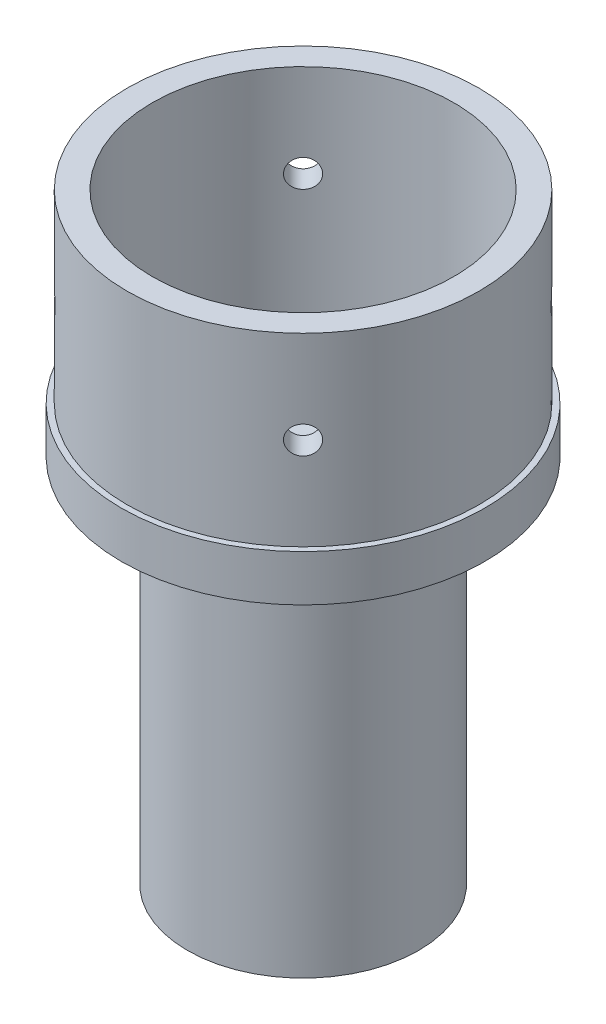
SolidWorks part; units mm, degrees
ref_plane "Front Plane" through (0, 0, 0) normal (0, 0, 1) x (1, 0, 0)
ref_plane "Top Plane" through (0, 0, 0) normal (0, 1, 0) x (1, 0, 0)
ref_plane "Right Plane" through (0, 0, 0) normal (1, 0, 0) x (0, 0, -1)
sketch "Sketch2" plane through (0, 0, 0) normal (0, 1, 0) x (1, 0, 0)
  circle A0 centre (0, 0) radius 19
  circle A1 centre (0, 0) radius 25
  dimension "D1" = 38
  dimension "D2" = 50
extrude "Boss-Extrude1" add sketch "Sketch2" along normal blind 70
sketch "Sketch3" plane through (0, 70, 0) normal (0, 1, 0) x (1, 0, 0)
  circle A0 centre (0, 0) radius 38.05
  circle A1 centre (0, 0) radius 32.6
  dimension "D1" = 76.1
extrude "Boss-Extrude2" add sketch "Sketch3" along normal blind 50 from offset 10 separate body
loft "Loft3" add section edge at (0, 70, 25) section edge at (0, 80, 38.05) connector at (-24.9573, 70, -1.46) connector at (-37.8357, 80, -4.0328)
loft "Cut-Loft1" cut section edge at (0, 70, 19) section edge at (0, 80, 32.6) connector at (-18.0957, 70, 5.7918) connector at (-21.2963, 80, 24.6825)
sketch "Sketch4" plane through (0, 130, 0) normal (0, 1, 0) x (1, 0, 0)
  circle A0 centre (0, 0) radius 38.05
  circle A1 centre (0, 0) radius 39.3
  dimension "D1" = 78.6
  dimension "D2" = 76.1
extrude "Boss-Extrude3" add sketch "Sketch4" along normal blind 10 from offset 50 offset against normal yes
ref_plane "Plane1" through (-26.9054, 0, 26.9054) normal (-0.7071, 0, 0.7071) x (0, -1, 0)
sketch "Sketch7" plane through (-26.9054, 0, 26.9054) normal (-0.7071, 0, 0.7071) x (0, -1, 0)
  line L0 (-130, 38.05) -> (-130, -38.05) construction
  circle A0 centre (-110, 0) radius 3
  dimension "D1" = 20
extrude "Cut-Extrude1" cut sketch "Sketch7" against normal up to next
pattern_circular "CirPattern1" count 4 over 360 about axis through (0, 130, 0) along (0, -1, 0) of "Cut-Extrude1" reverse direction yes
